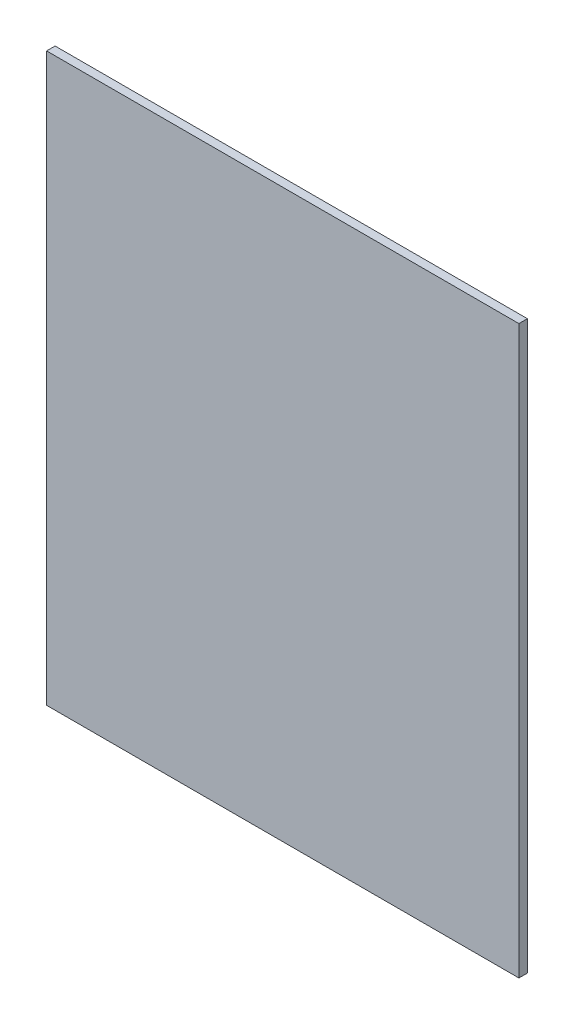
SolidWorks part; units mm, degrees
material "Pine"
ref_plane "Front Plane" through (0, 0, 0) normal (0, 0, 1) x (1, 0, 0)
ref_plane "Top Plane" through (0, 0, 0) normal (0, 1, 0) x (1, 0, 0)
ref_plane "Right Plane" through (0, 0, 0) normal (1, 0, 0) x (0, 0, -1)
sketch "Sketch1" plane through (0, 0, 0) normal (0, 0, 1) x (1, 0, 0)
  line L1 (-44.4031, 540.7123) -> (971.5969, 540.7123)
  line L2 (-44.4031, 540.7123) -> (-44.4031, -678.4877)
  line L3 (-44.4031, -678.4877) -> (971.5969, -678.4877)
  line L4 (971.5969, 540.7123) -> (971.5969, -678.4877)
  dimension "D1" = 1219.2
  dimension "D2" = 1016
extrude "Boss-Extrude1" add sketch "Sketch1" along normal blind 18.2562
sketch "Sketch2" plane through (0, 0, 18.2562) normal (0, 0, 1) x (1, 0, 0)
  line L0 (-44.4031, -678.4877) -> (971.5969, -678.4877) construction
  line L1 (-44.4031, 540.7123) -> (-44.4031, -678.4877) construction
  point P0 (88.1849, -545.9315)
  point P1 (88.1849, -469.7315)
  point P2 (164.3849, -545.9315)
  point P9 (762.8089, -545.9315)
  point P12 (839.0089, -469.7315)
  point P13 (839.0089, -545.9315)
  point P16 (839.0089, 408.156)
  point P17 (839.0089, 331.956)
  point P18 (762.8089, 408.156)
  point P19 (164.3849, 408.156)
  point P20 (88.1849, 331.956)
  point P21 (88.1849, 408.156)
  dimension "D1" = 132.5562
  dimension "D2" = 132.588
  dimension "D3" = 76.2
  dimension "D4" = 76.2
